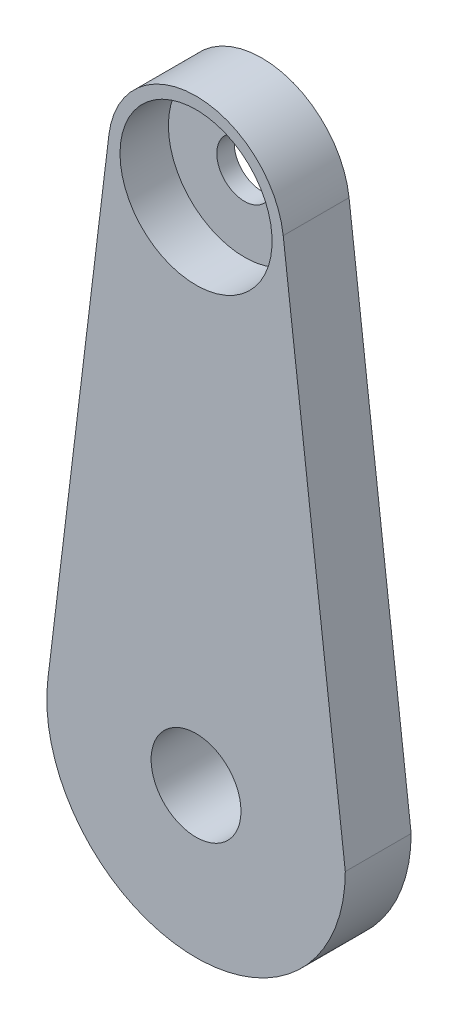
SolidWorks part; units mm, degrees
ref_plane "Front Plane" through (0, 0, 0) normal (0, 0, 1) x (1, 0, 0)
ref_plane "Top Plane" through (0, 0, 0) normal (0, 1, 0) x (1, 0, 0)
ref_plane "Right Plane" through (0, 0, 0) normal (1, 0, 0) x (0, 0, -1)
sketch "Sketch1" plane through (0, 0, 0) normal (0, 0, 1) x (1, 0, 0)
  line L0 (-12.6072, 75.1928) -> (-21.4322, 2.6057)
  line L1 (12.6103, 75.1665) -> (21.59, 0)
  circle A0 centre (0, 0) radius 11.05
  circle A1 centre (0, 0) radius 21.59
  circle A2 centre (0, 73.66) radius 11
  circle A3 centre (0, 73.66) radius 12.7
  dimension "D1" = 22.1
  dimension "D2" = 43.18
  dimension "D3" = 22
  dimension "D4" = 25.4
  dimension "D5" = 73.66
extrude "Boss-Extrude1" add sketch "Sketch1" along normal blind 9.525 contours A3 L0 A1 L1 | A3 A2 | L1 A1 A0 | A0 region at (-0.0627, 39.569, 0) region at (0.0129, 86.0008, 0) region at (-1.2247, 20.9436, 0)
extrude "Boss-Extrude2" add sketch "Sketch1<3>" along normal blind 2.5248 contours A2 region at (0, 73.66, 0)
sketch "Sketch1<3>" plane through (0, 0, 0) normal (0, 0, 1) x (1, 0, 0) same geometry as "Sketch1"
sketch "Sketch2" plane through (0, 0, 2.5248) normal (0, 0, 1) x (1, 0, 0)
  circle A0 centre (0, 73.66) radius 4
  dimension "D1" = 8
extrude "Cut-Extrude1" cut sketch "Sketch2" against normal blind 2.5248
sketch "Sketch3" plane through (0, 0, 9.525) normal (0, 0, 1) x (1, 0, 0)
  circle A0 centre (0, 0) radius 6.5
  dimension "D1" = 13
extrude "Cut-Extrude2" cut sketch "Sketch3" against normal through all
sketch "Sketch4" plane through (0, 0, 2.025) normal (0, 0, 1) x (1, 0, 0)
  circle A0 centre (0, 0) radius 3.045
  dimension "D1" = 6.09
